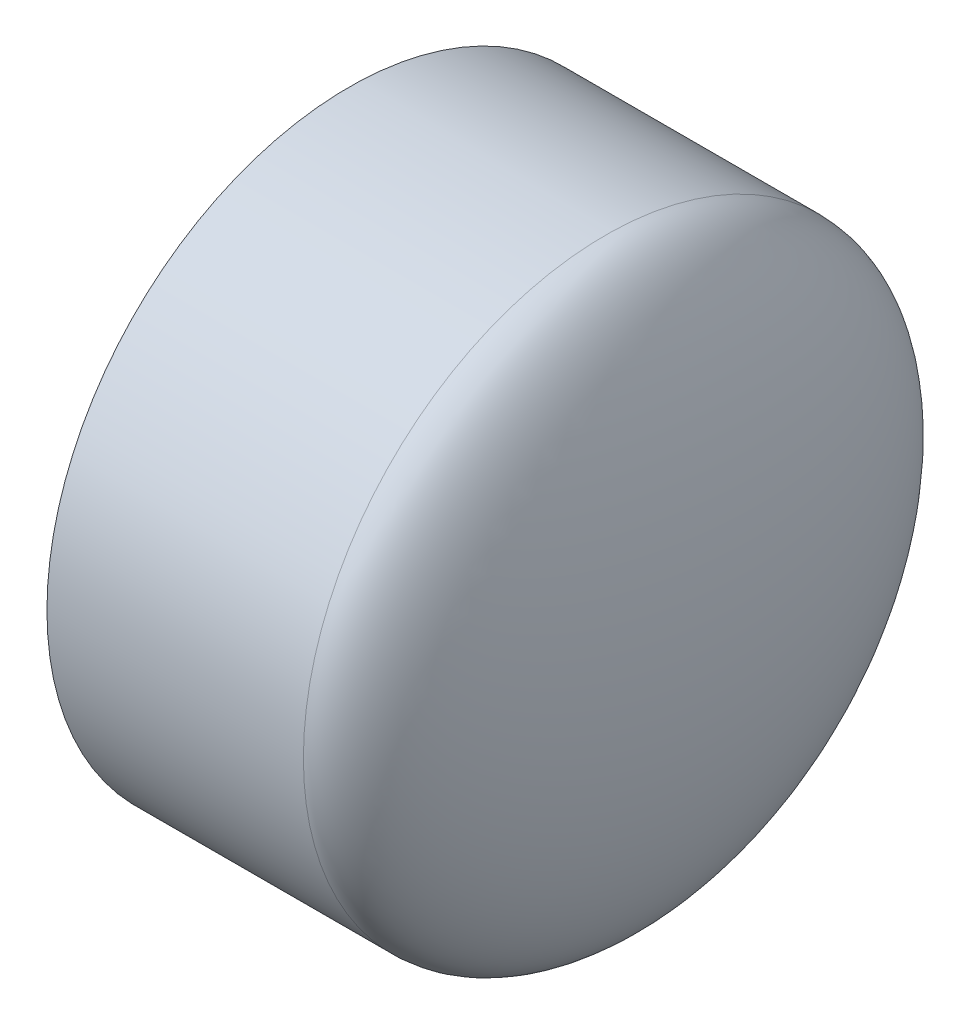
SolidWorks part; units mm, degrees
ref_plane "Front Plane" through (0, 0, 0) normal (0, 0, 1) x (1, 0, 0)
ref_plane "Top Plane" through (0, 0, 0) normal (0, 1, 0) x (1, 0, 0)
ref_plane "Right Plane" through (0, 0, 0) normal (1, 0, 0) x (0, 0, -1)
sketch "Sketch0" plane through (0, 0, 0) normal (0, 0, 1) x (1, 0, 0)
  line L0 (-79.1972, 0) -> (0, 0) construction
  line L2 (-22.0472, 0) -> (0, 0) construction
  line L4 (-79.1972, 67.31) -> (-79.1972, -67.31) construction
  line L5 (-22.0472, 57.0357) -> (-79.1972, 57.3786) construction
  line L6 (-22.0472, 57.0357) -> (-22.0472, -57.0357) construction
  line L7 (-22.0472, -57.0357) -> (-79.1972, -57.3786) construction
  line L8 (-79.1972, 57.3786) -> (-79.1972, -57.3786) construction
  line L14 (-22.0472, 48.5902) -> (-22.0472, -48.5902) construction
  dimension "M" = 134.62
  dimension "OD A" = 114.7572
  dimension "OD B" = 114.0714
  dimension "ID" = 97.1804
  dimension "W" = 79.1972
  dimension "C" = 57.15
sketch "Sketch1" plane through (0, 0, 0) normal (0, 0, 1) x (1, 0, 0)
  line L0 (-79.1972, 0) -> (0, 0) construction
  line L1 (-79.1972, 0) -> (0, 0) construction
  line L2 (-22.0472, 0) -> (0, 0) construction
  line L3 (-79.1972, -67.31) -> (-22.0472, -67.31)
  line L4 (-79.1972, -67.31) -> (-79.1972, -57.3786)
  line L5 (-79.1972, -57.3786) -> (-22.0472, -57.0357)
  line L6 (-22.0472, 0) -> (-22.0472, -57.0357) construction
  line L7 (-22.0472, -57.0357) -> (-22.0472, -67.31) construction
  line L8 (-10.2743, 0) -> (0, 0)
  ellipse E0 centre (-22.0472, 0) end of major axis (-22.0472, 67.31) minor radius 22.0472 (-22.0472, -67.31) -> (0, 0) ccw
  ellipse E1 centre (-22.0472, 0) end of major axis (-22.0472, -57.0357) minor radius 11.7729 (-22.0472, -57.0357) -> (-10.2743, 0) ccw
revolve "Revolve1" add sketch "Sketch1" angle 360 about L1
other "CPoint1" parameters "Diameter"=101.6, "StubLength"=114.3
ref_axis "Axis1" through (-32.0472, 0, 0) along (1, 0, 0)
other "RPoint1"
